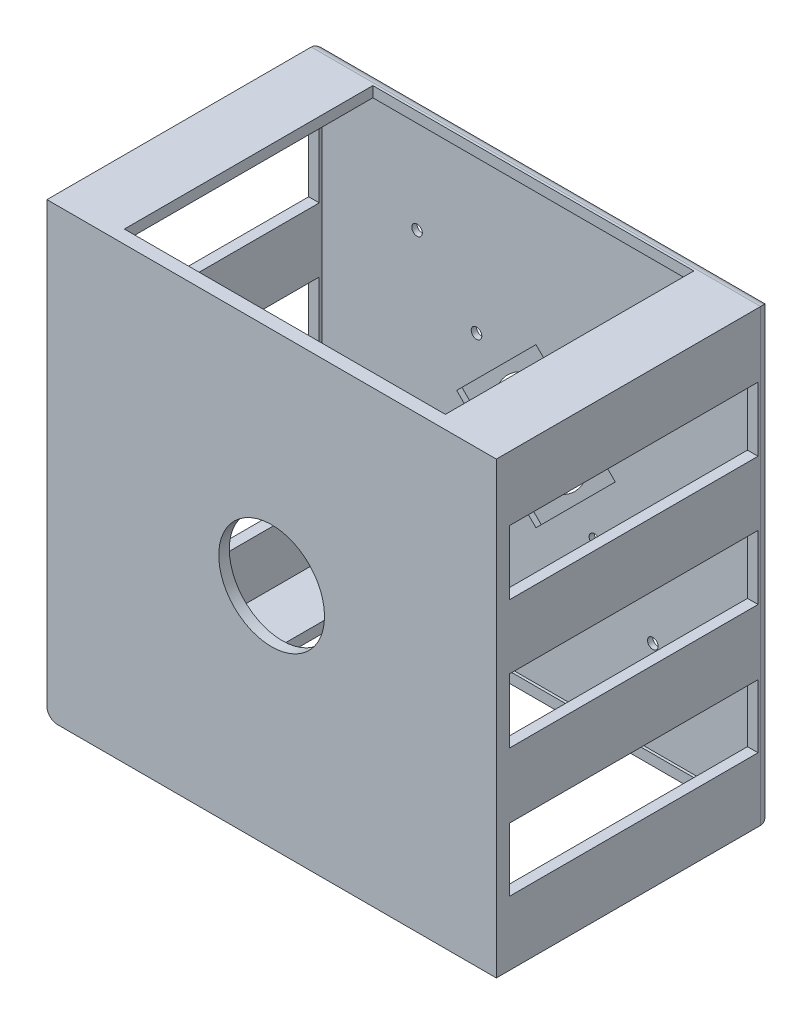
SolidWorks part; units mm, degrees
note: The reader was unsure of these and kept them because the rebuilt part matched: shared geometry of "草图1<3>".
ref_plane "前视基准面" through (0, 0, 0) normal (0, 0, 1) x (1, 0, 0)
ref_plane "上视基准面" through (0, 0, 0) normal (0, 1, 0) x (1, 0, 0)
ref_plane "右视基准面" through (0, 0, 0) normal (1, 0, 0) x (0, 0, -1)
sketch "草图1" plane through (0, 0, 0) normal (0, 0, 1) x (1, 0, 0)
  line L0 (67.6146, 20.3971) -> (67.6146, -60.6029)
  line L1 (-15.3854, 22.3971) -> (69.6146, 22.3971)
  line L2 (-15.3854, 22.3971) -> (-15.3854, -62.6029)
  line L3 (-15.3854, -62.6029) -> (69.6146, -62.6029)
  line L4 (69.6146, 22.3971) -> (69.6146, -62.6029)
  line L5 (-13.3854, -60.6029) -> (67.6146, -60.6029)
  line L6 (-13.3854, 20.3971) -> (-13.3854, -60.6029)
  line L7 (-13.3854, 20.3971) -> (67.6146, 20.3971)
  dimension "D1" = 2
extrude "凸台-拉伸1" add sketch "草图1" along normal blind 2 contours L1 L4 L3 L2
sketch "草图2" plane through (0, 0, 0) normal (0, 0, -1) x (-1, 0, 0)
  line L0 (-69.6146, -62.6029) -> (15.3854, 22.3971) construction
  circle A0 centre (-27.1146, -20.1029) radius 9
extrude "切除-拉伸1" cut sketch "草图2" against normal blind 2
sketch "草图3" plane through (0, 0, 2) normal (0, 0, 1) x (1, 0, 0)
  line L0 (27.1146, -20.1029) -> (4.6146, -20.1029) construction
  line L1 (4.6146, -20.1029) -> (4.6146, 2.3971) construction
  line L2 (4.6146, 2.3971) -> (27.1146, 2.3971) construction
  line L3 (27.1146, 2.3971) -> (49.6146, 2.3971) construction
  line L4 (49.6146, 2.3971) -> (49.6146, -20.495) construction
  line L5 (49.6146, -20.495) -> (49.6146, -42.995) construction
  line L6 (49.6146, -42.995) -> (27.1146, -42.995) construction
  line L7 (27.1146, -42.995) -> (4.6146, -42.995) construction
  line L8 (4.6146, -42.995) -> (4.6146, -20.1029) construction
  circle A0 centre (49.6146, -20.495) radius 5
  circle A1 centre (27.1146, 2.3971) radius 5
  circle A2 centre (27.1146, -42.995) radius 5
  circle A3 centre (4.6146, -20.1029) radius 5
sketch "草图4" plane through (0, 0, 0) normal (0, 0, -1) x (-1, 0, 0)
  line L0 (-27.1146, -20.1029) -> (-49.6146, 2.3971) construction
  line L1 (-49.6146, 2.3971) -> (-49.6146, -20.495) construction
  line L2 (-27.1146, 2.3971) -> (-49.6146, 2.3971) construction
  line L3 (-27.1146, -20.1029) -> (-4.6146, 2.3971) construction
  line L4 (-4.6146, 2.3971) -> (-27.1146, 2.3971) construction
  line L5 (-27.1146, -20.1029) -> (-4.6146, -42.6029) construction
  line L6 (-27.1146, -20.1029) -> (-49.2155, -42.995) construction
  line L7 (-49.6146, -42.995) -> (-27.1146, -42.995) construction
  circle A0 centre (-49.2155, -42.995) radius 5
  circle A1 centre (-38.165, -31.549) radius 5
  circle A2 centre (-49.6146, 2.3971) radius 5
  circle A3 centre (-38.3646, -8.8529) radius 5
  circle A4 centre (-4.6146, -42.6029) radius 5
  circle A5 centre (-15.8646, -31.3529) radius 5
  circle A6 centre (-4.6146, 2.3971) radius 5
  circle A7 centre (-15.8646, -8.8529) radius 5
extrude "切除-拉伸4" cut sketch "草图4" against normal blind 1
sketch "草图5" plane through (0, 0, 0) normal (0, 0, -1) x (-1, 0, 0)
  circle A0 centre (-4.6146, -42.6029) radius 1
  circle A1 centre (-15.8646, -31.3529) radius 1
  circle A2 centre (-15.8646, -8.8529) radius 1
  circle A3 centre (-4.6146, 2.3971) radius 1
  circle A4 centre (-38.3646, -8.8529) radius 1
  circle A5 centre (-49.6146, 2.3971) radius 1
  circle A7 centre (-49.2155, -42.995) radius 1
  circle A8 centre (-38.165, -31.549) radius 1
extrude "切除-拉伸5" cut sketch "草图5" against normal through all
extrude "凸台-拉伸2" add sketch "草图1<3>" along normal blind 50 contours L3 L4 L1 L2 | L5 L0 L7 L6
sketch "草图1<3>" plane through (0, 0, 0) normal (0, 0, 1) x (1, 0, 0) same geometry as "草图1"
ref_plane "基准面5" through (0, 0, 50) normal (0, 0, 1) x (1, 0, 0)
sketch "草图7" plane through (0, 0, 50) normal (0, 0, 1) x (1, 0, 0)
  line L1 (69.6146, -62.6029) -> (-15.3854, -62.6029)
  line L2 (69.6146, -62.6029) -> (69.6146, 22.3971)
  line L3 (69.6146, 22.3971) -> (-15.3854, 22.3971)
  line L4 (-15.3854, -62.6029) -> (-15.3854, 22.3971)
extrude "凸台-拉伸3" add sketch "草图7" along normal blind 2 contours L2 L3 L4 L1
sketch3d "3D草图1"
  line L0 (69.6146, 22.3971, 0) -> (69.6146, 22.3971, 2.5) construction
  line L1 (69.6146, 22.3971, 52) -> (69.6146, 22.3971, 0) construction
  line L2 (69.6146, 22.3971, 2.5) -> (-15.3854, 22.3971, 2.5)
  line L3 (-15.3854, 22.3971, 52) -> (-15.3854, 22.3971, 0) construction
  line L4 (-15.3854, 22.3971, 2.5) -> (-15.3854, -62.6029, 2.4973)
  line L5 (-15.3854, -62.6029, 52) -> (-15.3854, -62.6029, 0) construction
  line L6 (-15.3854, -62.6029, 2.4973) -> (69.6146, -62.6029, 2.4973)
  line L7 (69.6146, -62.6029, 52) -> (69.6146, -62.6029, 0) construction
  line L8 (69.6146, -62.6029, 2.4973) -> (69.6146, 22.3971, 2.5)
  line L9 (69.6146, 22.3971, 52) -> (69.6146, 22.3971, 49.5)
  line L10 (69.6146, 22.3971, 49.5) -> (-15.3854, 22.3971, 49.5)
  line L11 (-15.3854, 22.3971, 49.5) -> (-15.3854, -62.6029, 49.5)
  line L12 (-15.3854, -62.6029, 49.5) -> (69.6146, -62.6029, 49.5)
  line L13 (69.6146, -62.6029, 49.5) -> (69.6146, 22.3971, 49.5)
ref_point "点1"
ref_point "点2"
ref_point "点3"
ref_point "点4"
ref_point "点5"
ref_point "点6"
ref_point "点7"
ref_point "点8"
ref_point "点9"
ref_point "点10"
ref_point "点11"
ref_point "点12"
sketch "草图9" plane through (69.6146, 0, 0) normal (1, 0, 0) x (0, 0, -1)
  line L0 (-2.4977, -50.46) -> (-49.5, -50.46)
  line L1 (-49.5, -62.6029) -> (-49.5, 22.3971) construction
  line L2 (-2.4981, -38.4821) -> (-49.5, -38.4821)
  line L3 (-2.4973, -62.6029) -> (-2.5, 22.3971) construction
  line L4 (-2.4985, -26.1743) -> (-49.5, -26.1743)
  line L5 (-2.4989, -14.0315) -> (-49.5, -14.0315)
  line L6 (-2.4992, -1.8886) -> (-49.5, -1.8886)
  line L7 (-2.4996, 10.2542) -> (-49.5, 10.2542)
  line L8 (-2.4977, -50.46) -> (-2.4981, -38.4821)
  line L9 (-2.4985, -26.1743) -> (-2.4989, -14.0315)
  line L10 (-2.4992, -1.8886) -> (-2.4996, 10.2542)
  line L11 (-49.5, 10.2542) -> (-49.5, -1.8886)
  line L12 (-49.5, -14.0315) -> (-49.5, -26.1743)
  line L13 (-49.5, -38.4821) -> (-49.5, -50.46)
extrude "切除-拉伸6" cut sketch "草图9" against normal through all both and the other way through all
sketch "草图10" plane through (0, -62.6029, 0) normal (0, -1, 0) x (1, 0, 0)
  line L0 (-3.2425, 2.4973) -> (-3.2425, 49.5)
  line L1 (-15.3854, 49.5) -> (69.6146, 49.5) construction
  line L2 (-3.2425, 2.4973) -> (57.4717, 2.4973)
  line L3 (57.4717, 2.4973) -> (57.4717, 49.5)
  line L4 (57.4717, 49.5) -> (-3.2425, 49.5)
extrude "切除-拉伸7" cut sketch "草图10" against normal through all both and the other way through all
chamfer "倒角4" distance 1 angle 45 1 edges at (18.1146, -20.1029, 0)
fillet "圆角1" radius 2 4 edges at (27.1146, 22.3971, 0) (69.6146, -20.1029, 0) (27.1146, -62.6029, 0) (-15.3854, -20.1029, 0)
fillet "圆角2" radius 2 2 edges at (-14.7996, -62.0171, 0.5858) (-15.3854, -62.6029, 27)
sketch "草图11" plane through (0, 0, 52) normal (0, 0, 1) x (1, 0, 0)
  line L0 (69.6146, -20.1029) -> (-15.3854, -19.1029) construction
  line L1 (69.6146, -62.6029) -> (69.6146, 22.3971) construction
  line L2 (-15.3854, -60.6029) -> (-15.3854, 22.3971) construction
  circle A0 centre (27.1146, -19.6029) radius 10
extrude "切除-拉伸8" cut sketch "草图11" against normal blind 10
sketch "草图12" plane through (0, 0, 2) normal (0, 0, 1) x (1, 0, 0)
  line L0 (27.1146, -20.1029) -> (12.1146, -20.1029) construction
  line L1 (27.1146, -20.1029) -> (27.1146, -35.1029) construction
  line L2 (12.1146, -20.1029) -> (27.1146, -35.1029)
  line L3 (12.1146, -20.1029) -> (27.1146, -5.1029)
  line L4 (27.1146, -35.1029) -> (42.1146, -20.1029)
  line L5 (27.1146, -5.1029) -> (42.1146, -20.1029)
extrude "切除-拉伸9" cut sketch "草图12" against normal blind 1
